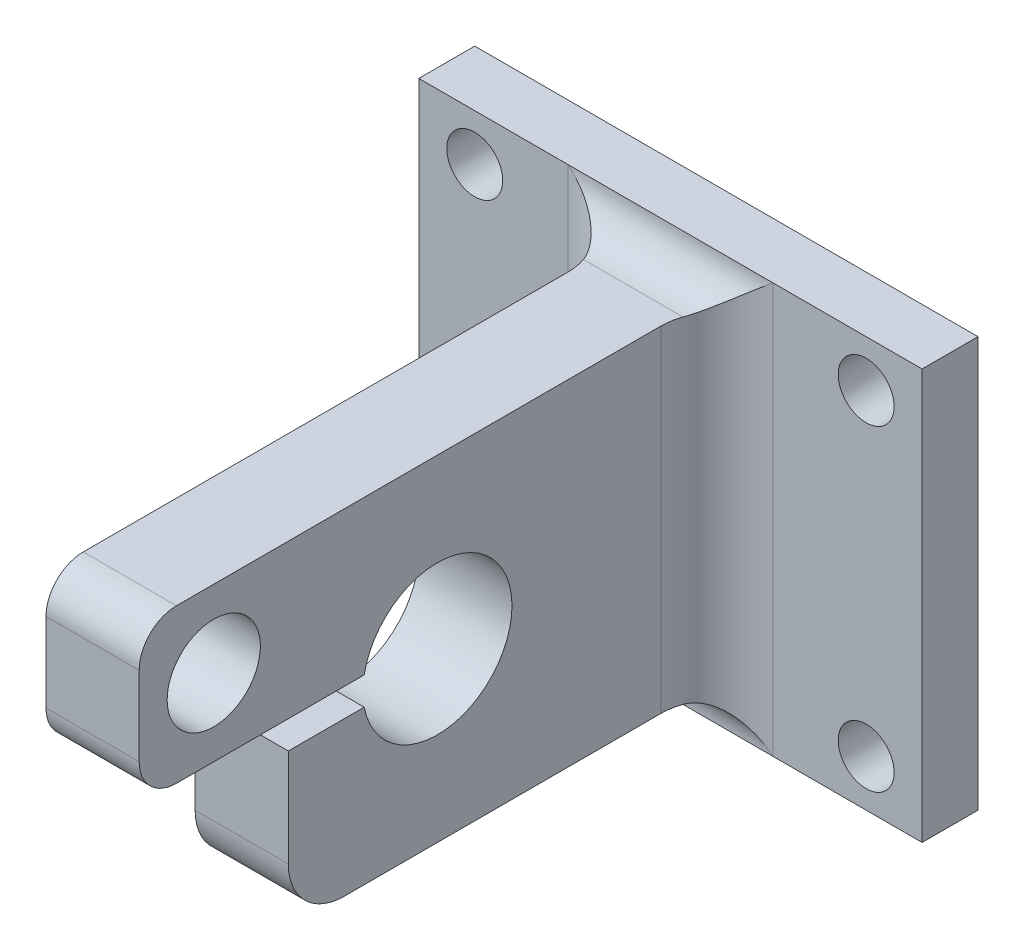
SolidWorks part; units mm, degrees
ref_plane "Front Plane" through (0, 0, 0) normal (0, 0, 1) x (1, 0, 0)
ref_plane "Top Plane" through (0, 0, 0) normal (0, 1, 0) x (1, 0, 0)
ref_plane "Right Plane" through (0, 0, 0) normal (1, 0, 0) x (0, 0, -1)
sketch "Sketch1" plane through (0, 0, 0) normal (0, 0, 1) x (1, 0, 0)
  line L1 (-13.5, -11) -> (13.5, -11)
  line L2 (-13.5, -11) -> (-13.5, 11)
  line L3 (-13.5, 11) -> (13.5, 11)
  line L4 (13.5, -11) -> (13.5, 11)
  line L5 (-13.5, -11) -> (13.5, 11) construction
  line L6 (-13.5, 11) -> (13.5, -11) construction
  line L7 (-10.5, -8.5) -> (-10.5, 8.5) construction
  line L8 (-10.5, 8.5) -> (10.5, 8.5) construction
  circle A5 centre (-10.5, -8.5) radius 1.5
  circle A6 centre (-10.5, 8.5) radius 1.5
  circle A7 centre (10.5, 8.5) radius 1.5
  circle A8 centre (10.5, -8.5) radius 1.5
  point P0 (0, 0)
  point P11 (-13.5, 0)
  point P12 (0, 11)
  point P13 (-10.5, 0)
  point P21 (0, 8.5)
  dimension "D5" = 3
  dimension "D1" = 27
  dimension "D2" = 22
  dimension "D6" = 17
  dimension "D7" = 21
extrude "Boss-Extrude1" add sketch "Sketch1" along normal blind 3
sketch "Sketch2" plane through (0, 0, 3) normal (0, 0, 1) x (1, 0, 0)
  line L1 (-2.5, 9) -> (2.5, 9)
  line L2 (-2.5, 9) -> (-2.5, -9)
  line L3 (-2.5, -9) -> (2.5, -9)
  line L4 (2.5, 9) -> (2.5, -9)
  line L5 (-13.5, -11) -> (13.5, -11) construction
  line L6 (2.5, 3.6093) -> (-2.5, 3.6093) construction
  line L7 (-13.5, 11) -> (-13.5, -11) construction
  point P4 (-13.5, 0)
  point P10 (0, -11)
  point P11 (0, 3.6093)
  point P16 (-2.5, 0)
  dimension "D1" = 5
  dimension "D2" = 18
extrude "Boss-Extrude2" add sketch "Sketch2" along normal blind 23
sketch "Sketch3" plane through (2.5, 0, 0) normal (1, 0, 0) x (0, 0, -1)
  line L0 (-26, -9) -> (-26, 9) construction
  line L1 (-3, -9) -> (-3, 9) construction
  circle A0 centre (-18, 0) radius 4
  point P5 (-26, 0)
  dimension "D1" = 8
  dimension "D2" = 15
extrude "Cut-Extrude1" cut sketch "Sketch3" against normal through all both and the other way through all
sketch "Sketch4" plane through (2.5, 0, 0) normal (1, 0, 0) x (0, 0, -1)
  line L1 (-26.2486, -0.75) -> (-16.7336, -0.75)
  line L2 (-26.2486, -0.75) -> (-26.2486, 0.75)
  line L3 (-26.2486, 0.75) -> (-16.7336, 0.75)
  line L4 (-16.7336, -0.75) -> (-16.7336, 0.75)
  line L5 (-26, -9) -> (-26, 9) construction
  point P6 (-26, 0)
  point P7 (-26.2486, 0)
  dimension "D1" = 1.5
extrude "Cut-Extrude2" cut sketch "Sketch4" against normal through all both and the other way through all
fillet "Fillet1" radius 3 2 edges at (-2.5, 0, 3) (2.5, 0, 3)
fillet "Fillet2" radius 2 2 edges at (0, 9, 3) (0, -9, 3)
fillet "Fillet3" radius 3 1 edges at (0, -9, 26)
sketch "Sketch6" plane through (-2.5, 0, 0) normal (-1, 0, 0) x (0, 0, 1)
  line L1 (26, 9) -> (34, 9)
  line L2 (26, 9) -> (26, 0.75)
  line L3 (26, 0.75) -> (34, 0.75)
  line L4 (34, 9) -> (34, 0.75)
  circle A0 centre (30, 4.875) radius 2.5
  point P8 (30, 0.75)
  point P9 (34, 4.875)
  dimension "D2" = 5
  dimension "D1" = 8
extrude "Boss-Extrude3" add sketch "Sketch6" against normal up to surface (5 mm away) up to face at (2.5, -0.7357, 19.5056)
fillet "Fillet4" radius 2 2 edges at (0, 0.75, 34) (0, 9, 34)
